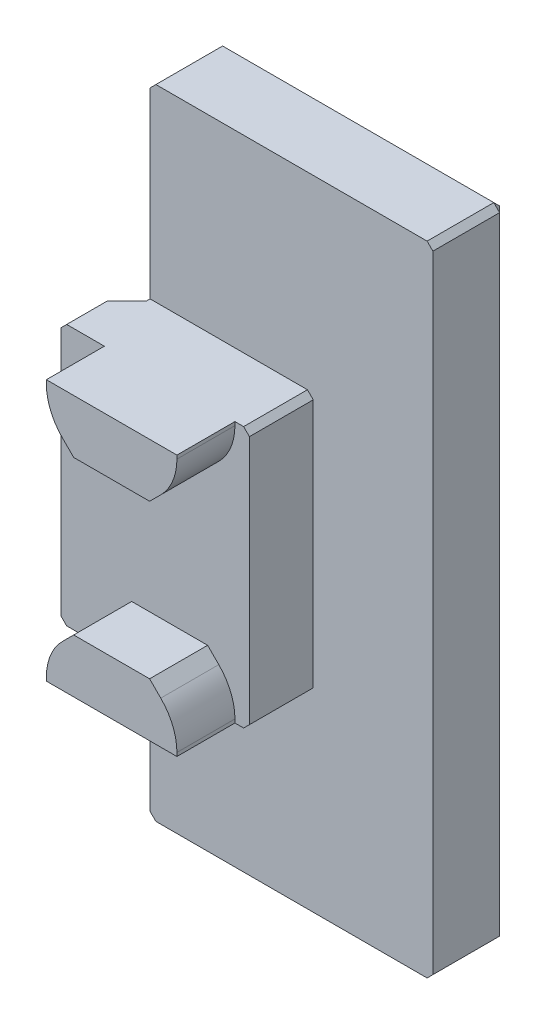
SolidWorks part; units mm, degrees
ref_plane "Front" through (0, 0, 0) normal (0, 0, 1) x (1, 0, 0)
ref_plane "Top" through (0, 0, 0) normal (0, 1, 0) x (1, 0, 0)
ref_plane "Right" through (0, 0, 0) normal (1, 0, 0) x (0, 0, -1)
sketch "Sketch1" plane through (0, 0, 0) normal (0, 0, 1) x (1, 0, 0)
  line L0 (-2.75, -11.5) -> (-2.75, -5) construction
  line L1 (2.75, -4.5) -> (-2.75, -4.5)
  line L2 (2.75, -4.5) -> (2.75, 4.5)
  line L3 (2.75, 4.5) -> (-2.75, 4.5)
  line L4 (-2.75, -4.5) -> (-2.75, 4.5) construction
  line L5 (2.75, -4.5) -> (-2.75, 4.5) construction
  line L6 (2.75, 4.5) -> (-2.75, -4.5) construction
  line L7 (-2.35, -4.5) -> (-3.75, -4.5) construction
  line L8 (-2.75, 4.5) -> (-3.75, 4.5)
  line L9 (-3.75, 4.5) -> (-3.75, -4.5)
  line L10 (-3.75, -4.5) -> (-2.75, -4.5)
  point P0 (0, 0)
extrude "Boss-Extrude1" add sketch "Sketch1" against normal blind 2
sketch "Sketch2" plane through (0, 0, 0) normal (0, 0, 1) x (1, 0, 0)
  line L0 (-2.25, -4.3784) -> (-2.25, -4.5)
  line L1 (-1.6935, -6.4651) -> (-1.3086, -6.85) construction
  line L2 (-1.3086, -6.85) -> (1.3086, -6.85) construction
  line L3 (1.3086, -6.85) -> (1.6935, -6.4651) construction
  line L4 (2.25, -5.1216) -> (2.25, -4.3784) construction
  line L5 (1.6935, -3.0349) -> (1.3086, -2.65)
  line L6 (1.3086, -2.65) -> (-1.3086, -2.65)
  line L7 (-1.3086, -2.65) -> (-1.6935, -3.0349)
  line L8 (-2.25, -4.3784) -> (-2.25, -5.1216) construction
  line L9 (1.35, -6.95) -> (1.7642, -6.5358)
  line L10 (-1.35, -6.95) -> (1.35, -6.95)
  line L11 (-1.7642, -6.5358) -> (-1.35, -6.95)
  line L12 (-2.35, -4.3784) -> (-2.35, -5.1216)
  line L13 (-1.35, -2.55) -> (-1.7642, -2.9642)
  line L14 (1.35, -2.55) -> (-1.35, -2.55)
  line L15 (1.7642, -2.9642) -> (1.35, -2.55)
  line L16 (2.35, -5.1216) -> (2.35, -4.3784)
  line L17 (1.35, -6.95) -> (1.7642, -6.5358) construction
  line L18 (-1.35, -6.95) -> (1.35, -6.95) construction
  line L20 (-1.7642, -6.5358) -> (-1.35, -6.95) construction
  line L22 (-2.35, -4.3784) -> (-2.35, -5.1216) construction
  line L24 (-1.35, -2.55) -> (-1.7642, -2.9642) construction
  line L26 (1.35, -2.55) -> (-1.35, -2.55) construction
  line L28 (1.7642, -2.9642) -> (1.35, -2.55) construction
  line L30 (2.35, -5.1216) -> (2.35, -4.3784) construction
  line L32 (2.25, -4.3784) -> (2.25, -4.5)
  line L39 (-2.75, -4.5) -> (2.75, -4.5)
  line L40 (-3.75, -4.5) -> (-2.75, -4.5)
  line L41 (-3.75, 4.5) -> (-3.75, -4.5)
  line L46 (-2.75, 4.5) -> (-3.75, 4.5)
  line L48 (2.75, 4.5) -> (-2.75, 4.5)
  line L54 (2.75, -4.5) -> (2.75, 4.5)
  line L58 (-2.25, -4.5) -> (2.25, -4.5)
  arc A0 (-2.25, -5.1216) -> (-1.6935, -6.4651) centre (-0.35, -5.1216) ccw construction
  arc A2 (1.6935, -6.4651) -> (2.25, -5.1216) centre (0.35, -5.1216) ccw construction
  arc A4 (2.25, -4.3784) -> (1.6935, -3.0349) centre (0.35, -4.3784) ccw
  arc A5 (-1.6935, -3.0349) -> (-2.25, -4.3784) centre (-0.35, -4.3784) ccw
  arc A7 (-2.35, -5.1216) -> (-1.7642, -6.5358) centre (-0.35, -5.1216) ccw
  arc A8 (-1.7642, -2.9642) -> (-2.35, -4.3784) centre (-0.35, -4.3784) ccw
  arc A10 (2.35, -4.3784) -> (1.7642, -2.9642) centre (0.35, -4.3784) ccw
  arc A11 (1.7642, -6.5358) -> (2.35, -5.1216) centre (0.35, -5.1216) ccw
  arc A12 (-2.35, -5.1216) -> (-1.7642, -6.5358) centre (-0.35, -5.1216) ccw construction
  arc A13 (-1.7642, -2.9642) -> (-2.35, -4.3784) centre (-0.35, -4.3784) ccw construction
  arc A14 (2.35, -4.3784) -> (1.7642, -2.9642) centre (0.35, -4.3784) ccw construction
  arc A15 (1.7642, -6.5358) -> (2.35, -5.1216) centre (0.35, -5.1216) ccw construction
  dimension "D1" = 0
  dimension "D2" = 0.1
  dimension "D3" = 0
extrude "Slot Tab" add sketch "Sketch2" along normal blind 2 contours L7 A5 L0 L58 L32 A4 L5 L6 region at (0, -3.648, 0)
mirror "Slot Tabs" about plane through (0, 0, 0) normal (0, 1, 0) of "Slot Tab"
chamfer "Deburs" [suppressed] distance 0.2 angle 45
sketch "Sketch3" plane through (0, 0, -2) normal (0, 0, -1) x (-1, 0, 0)
  line L4 (3.75, 4.5) -> (-2.75, 4.5)
  line L5 (-2.75, 4.5) -> (-2.75, -4.5)
  line L6 (-2.75, -4.5) -> (3.75, -4.5)
  line L7 (3.75, -4.5) -> (3.75, 4.5)
  line L8 (3.75, 4.5) -> (-2.75, 4.5)
  line L9 (-2.75, 4.5) -> (-2.75, -4.5)
  line L10 (-2.75, -4.5) -> (3.75, -4.5)
  line L11 (3.75, -4.5) -> (3.75, 4.5)
  dimension "D1" = 0
extrude "Stopper Clearance" add sketch "Sketch3" along normal blind 0.2
sketch "Sketch4" plane through (0, 0, -2.2) normal (0, 0, -1) x (-1, 0, 0)
  line L1 (2.875, -11) -> (-6.875, -11)
  line L2 (2.875, -11) -> (2.875, 11)
  line L3 (2.875, 11) -> (-6.875, 11)
  line L4 (-6.875, -11) -> (-6.875, 11)
  line L5 (2.875, -11) -> (-6.875, 11) construction
  line L6 (2.875, 11) -> (-6.875, -11) construction
  point P0 (-2, 0)
  dimension "D1" = 2
  dimension "D2" = 22
  dimension "D3" = 9.75
extrude "Stopper" add sketch "Sketch4" along normal blind 2.5
chamfer "Deburs 2" distance 0.2 angle 45 12 edges at (2.75, 4.5, -1.1) (2.75, -4.5, -1.1) (-3.75, -4.5, -1.1) (-3.75, 4.5, -1.1) (2, 11, -4.7) (-2.875, 11, -3.45) (-2.875, 0, -4.7) (6.875, 11, -3.45) (6.875, 0, -4.7) (6.875, -11, -3.45) (2, -11, -4.7) (-2.875, -11, -3.45)
chamfer "Chamfer3" distance 1 angle 45 1 edges at (-3.75, 0, -2.2)
